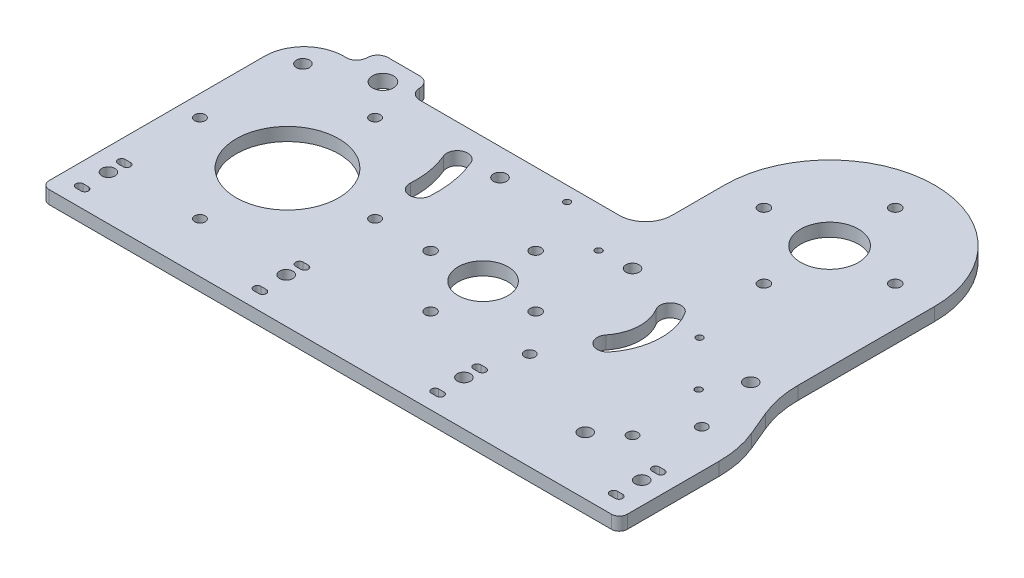
SolidWorks part; units mm, degrees
material "6061 Alloy"
ref_plane "Front Plane" through (0, 0, 0) normal (0, 0, 1) x (1, 0, 0)
ref_plane "Top Plane" through (0, 0, 0) normal (0, 1, 0) x (1, 0, 0)
ref_plane "Right Plane" through (0, 0, 0) normal (1, 0, 0) x (0, 0, -1)
sketch "Sketch1" plane through (0, 0, 0) normal (0, 1, 0) x (1, 0, 0)
  line L0 (0, 0) -> (190, 0)
  line L1 (210, 70) -> (210, 130)
  line L2 (130, 130) -> (130, 110)
  line L3 (120, 100) -> (15, 100)
  line L4 (0, 85) -> (0, 0)
  line L5 (41.3, 81.8789) -> (41.3, 71.8789) construction
  line L6 (41.3, 71.8789) -> (41.3, 52.3789) construction
  line L7 (41.3, 52.3789) -> (8.8, 52.3789) construction
  line L8 (17.63, 76.0489) -> (64.97, 76.0489) construction
  line L9 (17.63, 76.0489) -> (17.63, 28.7089) construction
  line L10 (17.63, 28.7089) -> (64.97, 28.7089) construction
  line L11 (64.97, 76.0489) -> (64.97, 28.7089) construction
  line L12 (17.63, 76.0489) -> (64.97, 28.7089) construction
  line L13 (17.63, 28.7089) -> (64.97, 76.0489) construction
  line L14 (190, 0) -> (0, 0)
  line L16 (220, 0) -> (190, 0)
  line L17 (220, 0) -> (220, 29.75)
  line L18 (220, 29.75) -> (220, 46)
  line L19 (220, 46) -> (210, 70)
  arc A0 (210, 130) -> (130, 130) centre (170, 130) ccw
  arc A1 (15, 100) -> (0, 85) centre (15, 85) ccw
  arc A2 (130, 110) -> (120, 100) centre (120, 110) cw
  circle A3 centre (170, 130) radius 11
  circle A4 centre (170, 130) radius 25 construction
  circle A5 centre (170, 105) radius 2.1
  circle A9 centre (115.75, 52.3789) radius 9.5
  circle A10 centre (41.3, 52.3789) radius 19
  circle A11 centre (41.3, 52.3789) radius 19.5
  circle A12 centre (17.63, 76.0489) radius 2.1 construction
  circle A13 centre (64.97, 76.0489) radius 2.1 construction
  circle A14 centre (64.97, 28.7089) radius 2.1 construction
  circle A15 centre (17.63, 28.7089) radius 2.1 construction
  circle A16 centre (9.8356, 89.7253) radius 2.5
  circle A17 centre (84.8356, 89.7253) radius 2.5
  circle A18 centre (200, 70) radius 2.5
  circle A22 centre (145, 130) radius 2.1
  circle A23 centre (170, 155) radius 2.1
  circle A24 centre (195, 130) radius 2.1
  circle A25 centre (115.75, 72.3789) radius 2.1
  circle A26 centre (115.75, 52.3789) radius 9.5
  circle A27 centre (135.75, 52.3789) radius 2.1
  circle A28 centre (115.75, 52.3789) radius 9.5
  circle A29 centre (115.75, 32.3789) radius 2.1
  circle A30 centre (115.75, 52.3789) radius 9.5
  circle A31 centre (95.75, 52.3789) radius 2.1
  circle A32 centre (185, 22) radius 2.5
  circle A33 centre (140, 85) radius 2.5
  circle A35 centre (105.6349, 94.474) radius 1.25
  circle A36 centre (127.6349, 84.474) radius 1.25
  circle A37 centre (175.5515, 74.952) radius 1.25
  circle A38 centre (192.4728, 57.699) radius 1.25
  arc A39 (161.3606, 78.0699) -> (160, 55.58) centre (144.5266, 67.8022) cw construction
  arc A40 (163.1389, 53.1007) -> (164.7755, 80.1528) centre (144.5266, 67.8022) ccw
  arc A41 (156.8611, 58.0594) -> (157.9457, 75.987) centre (144.5266, 67.8022) ccw
  arc A42 (156.8611, 58.0594) -> (163.1389, 53.1007) centre (160, 55.58) ccw
  arc A43 (164.7755, 80.1528) -> (157.9457, 75.987) centre (161.3606, 78.0699) ccw
  arc A44 (73.5517, 70.6327) -> (70.6203, 87.6705) centre (36.4824, 73.0259) ccw construction
  arc A45 (77.5434, 70.375) -> (74.2963, 89.2474) centre (36.4824, 73.0259) ccw
  arc A46 (69.56, 70.8904) -> (66.9442, 86.0935) centre (36.4824, 73.0259) ccw
  arc A47 (69.56, 70.8904) -> (77.5434, 70.375) centre (73.5517, 70.6327) ccw
  arc A48 (74.2963, 89.2474) -> (66.9442, 86.0935) centre (70.6203, 87.6705) ccw
  circle A49 centre (148.6368, 37.2332) radius 2
  circle A50 centre (195, 30) radius 2
  circle A51 centre (205.3659, 46) radius 2
  point P27 (160, 125)
  point P28 (160, 130)
  point P46 (36.3, 48)
  point P54 (170, 130)
  point P67 (115.75, 52.3789)
  point P86 (164.2088, 66.6115)
  point P92 (73.0909, 79.3245)
  dimension "D3" = 40
  dimension "D4" = 10
  dimension "D6" = 22
  dimension "D7" = 4.2
  dimension "D9" = 19
  dimension "D10" = 38
  dimension "D17" = 22
  dimension "D18" = 4.2
  dimension "D19" = 35
  dimension "D20" = 130
  dimension "D21" = 5
  dimension "D28" = 50
  dimension "D30" = 4.2
  dimension "D39" = 4
  dimension "D42" = 2.5
  dimension "D43" = 2.5
  dimension "D40" = 4
  dimension "D41" = 4
  dimension "D44" = 25
  dimension "D45" = 30
  dimension "D1" = 190
  dimension "D5" = 105
  dimension "D8" = 74.45
  dimension "D11" = 41.3
  dimension "D12" = 85
  dimension "D13" = 10
  dimension "D14" = 19.5
  dimension "D15" = 47.34
  dimension "D16" = 47.34
  dimension "D22" = 7
  dimension "D23" = 75
  dimension "D24" = 10
  dimension "D25" = 70
  dimension "D27" = 30
  dimension "D29" = 94.7
  dimension "D31" = 20
  dimension "D33" = 46
  dimension "D34" = 50
  dimension "D35" = 115.75
  dimension "D36" = 52.3789
  dimension "D37" = 70
  dimension "D38" = 85
  dimension "D26" = 4
  dimension "D32" = 4
extrude "Boss-Extrude1" add sketch "Sketch1" along normal blind 5
extrude "Cut-Extrude1" cut sketch "Sketch2" against normal mid plane 200
sketch "Sketch2" plane through (300.1958, -95, 207.7966) normal (0, 1, 0) x (1, 0, 0)
  line L1 (-87.4826, 230.7966) -> (-89.4826, 230.7966) construction
  line L2 (-87.4826, 229.5466) -> (-89.4826, 229.5466)
  line L3 (-87.4826, 232.0466) -> (-89.4826, 232.0466)
  line L4 (-87.4826, 214.7966) -> (-89.4826, 214.7966) construction
  line L5 (-87.4826, 213.5466) -> (-89.4826, 213.5466)
  line L6 (-87.4826, 216.0466) -> (-89.4826, 216.0466)
  circle A0 centre (371.201, 492.148) radius 2.5
  arc A1 (-87.4826, 229.5466) -> (-87.4826, 232.0466) centre (-87.4826, 230.7966) ccw
  arc A2 (-89.4826, 232.0466) -> (-89.4826, 229.5466) centre (-89.4826, 230.7966) ccw
  arc A3 (-87.4826, 213.5466) -> (-87.4826, 216.0466) centre (-87.4826, 214.7966) ccw
  arc A4 (-89.4826, 216.0466) -> (-89.4826, 213.5466) centre (-89.4826, 214.7966) ccw
  point P7 (-88.4826, 230.7966)
  point P12 (-88.4826, 214.7966)
sketch "Sketch15" plane through (0, 5, 0) normal (0, 1, 0) x (1, 0, 0)
  circle A0 centre (41.3, 52.3789) radius 33.333 construction
  circle A1 centre (41.3, 85.712) radius 2
  circle A2 centre (74.633, 52.3789) radius 2
  circle A3 centre (41.3, 19.0459) radius 2
  circle A4 centre (7.967, 52.3789) radius 2
  point P14 (41.3, 52.3789)
  dimension "D1" = 4
  dimension "D2" = 4
extrude "Cut-Extrude14" cut sketch "Sketch15" against normal blind 10
sketch "Sketch17" [suppressed] plane through (0, 5, 0) normal (0, 1, 0) x (1, 0, 0)
  line L0 (210.7132, 23) -> (212.7132, 23) construction
  line L1 (210.7132, 24.3615) -> (212.7132, 24.3615)
  line L2 (210.7132, 21.6385) -> (212.7132, 21.6385)
  line L3 (210.7132, 7) -> (212.7132, 7) construction
  line L4 (210.7132, 8.3119) -> (212.7132, 8.3119)
  line L5 (210.7132, 5.6881) -> (212.7132, 5.6881)
  circle A0 centre (211.7132, 15) radius 2.5
  arc A1 (210.7132, 24.3615) -> (210.7132, 21.6385) centre (210.7132, 23) ccw
  arc A2 (212.7132, 21.6385) -> (212.7132, 24.3615) centre (212.7132, 23) ccw
  arc A3 (210.7132, 8.3119) -> (210.7132, 5.6881) centre (210.7132, 7) ccw
  arc A4 (212.7132, 5.6881) -> (212.7132, 8.3119) centre (212.7132, 7) ccw
  point P7 (211.7132, 23)
  point P16 (211.7132, 7)
extrude "Boss-Extrude2" [suppressed] add sketch "Sketch17" against normal blind 5
extrude "Cut-Extrude15" cut sketch "Sketch18" against normal through all
sketch "Sketch18" plane through (300.638, 0, 207.7972) normal (0, -1, 0) x (-1, 0, 0)
  line L1 (293.118, 230.7972) -> (291.118, 230.7972) construction
  line L2 (293.118, 229.3972) -> (291.118, 229.3972)
  line L3 (293.118, 232.1972) -> (291.118, 232.1972)
  line L4 (293.118, 214.7972) -> (291.118, 214.7972) construction
  line L5 (293.118, 213.3972) -> (291.118, 213.3972)
  line L6 (293.118, 216.1972) -> (291.118, 216.1972)
  line L7 (225.458, 230.7972) -> (223.458, 230.7972) construction
  line L8 (225.458, 229.3972) -> (223.458, 229.3972)
  line L9 (225.458, 232.1972) -> (223.458, 232.1972)
  line L10 (225.458, 214.7972) -> (223.458, 214.7972) construction
  line L11 (225.458, 213.3972) -> (223.458, 213.3972)
  line L12 (225.458, 216.1972) -> (223.458, 216.1972)
  line L13 (157.798, 230.7972) -> (155.798, 230.7972) construction
  line L14 (157.798, 229.3972) -> (155.798, 229.3972)
  line L15 (157.798, 232.1972) -> (155.798, 232.1972)
  line L16 (157.798, 214.7972) -> (155.798, 214.7972) construction
  line L17 (157.798, 213.3972) -> (155.798, 213.3972)
  line L18 (157.798, 216.1972) -> (155.798, 216.1972)
  line L19 (90.138, 231.0972) -> (88.138, 231.0972) construction
  line L20 (90.138, 229.6972) -> (88.138, 229.6972)
  line L21 (90.138, 232.4972) -> (88.138, 232.4972)
  line L22 (90.138, 215.0972) -> (88.138, 215.0972) construction
  line L23 (90.138, 213.6972) -> (88.138, 213.6972)
  line L24 (90.138, 216.4972) -> (88.138, 216.4972)
  circle A0 centre (292.118, 224.7972) radius 2.5
  arc A1 (293.118, 229.3972) -> (293.118, 232.1972) centre (293.118, 230.7972) ccw
  arc A2 (291.118, 232.1972) -> (291.118, 229.3972) centre (291.118, 230.7972) ccw
  arc A3 (293.118, 213.3972) -> (293.118, 216.1972) centre (293.118, 214.7972) ccw
  arc A4 (291.118, 216.1972) -> (291.118, 213.3972) centre (291.118, 214.7972) ccw
  circle A5 centre (224.458, 224.7972) radius 2.5
  arc A6 (225.458, 229.3972) -> (225.458, 232.1972) centre (225.458, 230.7972) ccw
  arc A7 (223.458, 232.1972) -> (223.458, 229.3972) centre (223.458, 230.7972) ccw
  arc A8 (225.458, 213.3972) -> (225.458, 216.1972) centre (225.458, 214.7972) ccw
  arc A9 (223.458, 216.1972) -> (223.458, 213.3972) centre (223.458, 214.7972) ccw
  circle A10 centre (156.798, 224.7972) radius 2.5
  arc A11 (157.798, 229.3972) -> (157.798, 232.1972) centre (157.798, 230.7972) ccw
  arc A12 (155.798, 232.1972) -> (155.798, 229.3972) centre (155.798, 230.7972) ccw
  arc A13 (157.798, 213.3972) -> (157.798, 216.1972) centre (157.798, 214.7972) ccw
  arc A14 (155.798, 216.1972) -> (155.798, 213.3972) centre (155.798, 214.7972) ccw
  circle A15 centre (89.138, 224.7972) radius 2.5
  arc A16 (90.138, 229.6972) -> (90.138, 232.4972) centre (90.138, 231.0972) ccw
  arc A17 (88.138, 232.4972) -> (88.138, 229.6972) centre (88.138, 231.0972) ccw
  arc A18 (90.138, 213.6972) -> (90.138, 216.4972) centre (90.138, 215.0972) ccw
  arc A19 (88.138, 216.4972) -> (88.138, 213.6972) centre (88.138, 215.0972) ccw
  point P7 (292.118, 230.7972)
  point P12 (292.118, 214.7972)
  point P26 (224.458, 230.7972)
  point P31 (224.458, 214.7972)
  point P42 (156.798, 230.7972)
  point P47 (156.798, 214.7972)
  point P58 (89.138, 231.0972)
  point P63 (89.138, 215.0972)
  dimension "D1" = 1.4
  dimension "D2" = 1.4
fillet "Fillet2" radius 40 1 edges at (210, 2.5, -70)
fillet "Fillet3" radius 40 1 edges at (220, 2.5, -46)
extrude "Cut-Extrude16" cut sketch "Sketch19" against normal through all
sketch "Sketch19" plane through (300.1958, 5, 207.7966) normal (0, 1, 0) x (1, 0, 0)
  line L0 (-265.3517, 298.1022) -> (-261.5739, 294.3244)
  line L1 (-293.2736, 270.1803) -> (-265.3517, 298.1022)
  line L2 (-293.3814, 257.1607) -> (-265.4596, 229.2388)
  line L3 (-252.3321, 297.9943) -> (-224.4102, 270.0725)
  line L4 (-252.44, 229.131) -> (-224.5181, 257.0528)
  line L5 (-299.6216, 263.6166) -> (-217.7387, 263.6166) construction
  line L6 (-258.764, 304.5642) -> (-259.0276, 222.7011) construction
  line L9 (-256.112, 294.2186) -> (-252.3321, 297.9943)
  line L11 (-228.2938, 260.8327) -> (-224.5181, 257.0528)
  line L12 (-224.4102, 270.0725) -> (-228.188, 266.2947)
  line L14 (-261.6797, 233.0145) -> (-265.4596, 229.2388)
  line L15 (-252.44, 229.131) -> (-256.2177, 232.9088)
  line L16 (-289.4979, 266.4004) -> (-293.2736, 270.1803)
  line L17 (-293.3814, 257.1607) -> (-289.6036, 260.9385)
  arc A1 (-261.5739, 294.3244) -> (-256.112, 294.2186) centre (-258.788, 297.1103) ccw
  arc A2 (-228.188, 266.2947) -> (-228.2938, 260.8327) centre (-225.4021, 263.5087) ccw
  arc A3 (-256.2177, 232.9088) -> (-261.6797, 233.0145) centre (-259.0037, 230.1228) ccw
  arc A4 (-289.6036, 260.9385) -> (-289.4979, 266.4004) centre (-292.3896, 263.7244) ccw
  point P3 (-258.8958, 263.6166)
  point P39 (-258.8958, 263.6166)
sketch "Sketch21" plane through (0, 0, 0) normal (0, -1, 0) x (1, 0, 0)
  line L0 (120, -100) -> (15, -100) construction
  line L1 (20, -100) -> (40, -100)
  line L2 (20, -100) -> (20, -108)
  line L3 (20, -108) -> (40, -108)
  line L4 (40, -100) -> (40, -108)
  dimension "D1" = 20
  dimension "D2" = 5
  dimension "D3" = 8
extrude "Boss-Extrude3" add sketch "Sketch21" against normal blind 5
sketch "Sketch20" plane through (0, 0, 0) normal (0, -1, 0) x (-1, 0, 0)
  line L0 (-60.5431, 55.5337) -> (-106.7891, 55.5337) construction
  line L1 (-83.6661, 41.0934) -> (-83.6661, 69.9739) construction
  circle A0 centre (-41.3, 52.3789) radius 19.5 construction
  circle A1 centre (-115.75, 52.3789) radius 9.5 construction
  circle A5 centre (-31, 99) radius 4
  point P9 (-83.6661, 55.5337)
extrude "Cut-Extrude17" cut sketch "Sketch20" against normal through all
fillet "Fillet4" radius 4 4 edges at (40, 2.5, -108) (40, 2.5, -100) (20, 2.5, -108) (20, 2.5, -100)
sketch "Sketch22" plane through (0, 0, 0) normal (0, -1, 0) x (-1, 0, 0)
fillet "Fillet5" radius 3 2 edges at (220, 2.5, 0) (0, 2.5, 0)
